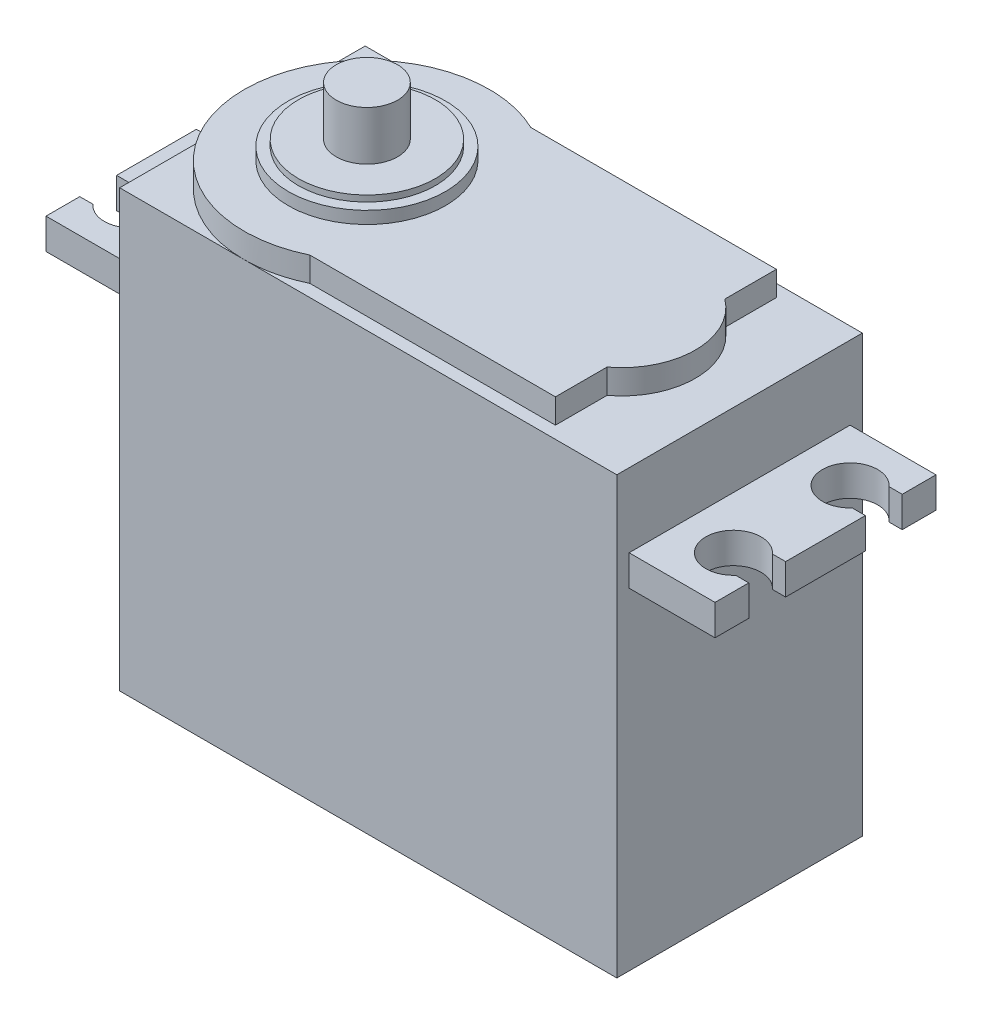
SolidWorks part; units mm, degrees
ref_plane "Front" through (0, 0, 0) normal (0, 0, 1) x (1, 0, 0)
ref_plane "Top" through (0, 0, 0) normal (0, 1, 0) x (1, 0, 0)
ref_plane "Right" through (0, 0, 0) normal (1, 0, 0) x (0, 0, -1)
sketch "Sketch1" plane through (0, 0, 0) normal (0, 1, 0) x (1, 0, 0)
  line L0 (-20.25, 10) -> (20.25, -10) construction
  line L1 (-20.25, -10) -> (20.25, -10)
  line L2 (-20.25, -10) -> (-20.25, 10)
  line L3 (-20.25, 10) -> (20.25, 10)
  line L4 (20.25, -10) -> (20.25, 10)
  line L5 (20.25, 10) -> (-20.25, -10) construction
  dimension "D1" = 20
  dimension "D2" = 40.5
extrude "Boss-Extrude1" add sketch "Sketch1" along normal blind 35.5
sketch "Sketch2" plane through (0, 35.5, 0) normal (0, 1, 0) x (1, 0, 0)
  line L0 (-5.75, -9) -> (14.25, -9)
  line L1 (14.25, -9) -> (14.25, -4.8)
  line L2 (-5.75, 9) -> (14.25, 9)
  line L3 (14.25, 9) -> (14.25, 4.8)
  line L4 (20.25, 10) -> (-20.25, 10) construction
  line L5 (-20.25, -10) -> (20.25, -10) construction
  line L6 (20.25, -10) -> (20.25, 10) construction
  line L7 (20.25, -10) -> (20.25, 10) construction
  arc A0 (-5.75, 9) -> (-5.75, -9) centre (-10.1089, 0) ccw
  arc A1 (14.25, 4.8) -> (14.25, -4.8) centre (10.65, 0) cw
  point P6 (0, 10)
  point P12 (16.65, 0)
  point P13 (20.25, 0)
  dimension "D1" = 1
  dimension "D3" = 4.2
  dimension "D2" = 1
  dimension "D4" = 3.6
  dimension "D5" = 20
  dimension "D6" = 6
extrude "Boss-Extrude2" add sketch "Sketch2" along normal blind 2
sketch "Sketch3" plane through (0, 37.5, 0) normal (0, 1, 0) x (1, 0, 0)
  circle A0 centre (-10.1089, 0) radius 6.4
  arc A1 (-10.1089, 10) -> (-10.1089, -10) centre (-10.1089, 0) ccw construction
  dimension "D1" = 12.8
extrude "Boss-Extrude3" add sketch "Sketch3" along normal blind 1
sketch "Sketch4" plane through (0, 38.5, 0) normal (0, 1, 0) x (1, 0, 0)
  circle A0 centre (-10.1089, 0) radius 5.575
  circle A1 centre (-10.1089, 0) radius 6.4 construction
  dimension "D1" = 11.15
extrude "Boss-Extrude4" add sketch "Sketch4" along normal blind 0.5
ref_plane "Plane1" through (0, 29.5, 0) normal (0, 1, 0) x (1, 0, 0)
sketch "Sketch5" plane through (0, 29.5, 0) normal (0, 1, 0) x (1, 0, 0)
  line L0 (20.25, 9) -> (27.25, 9)
  line L1 (20.25, -10) -> (20.25, 10) construction
  line L2 (27.25, 0) -> (27.25, 3.25)
  line L3 (20.25, 0) -> (27.25, 0)
  line L4 (20.25, 0) -> (20.25, 9)
  line L5 (20.25, 10) -> (-10.1089, 10) construction
  line L7 (24.5, 7) -> (24.5, 9) construction
  line L8 (27.25, 6.25) -> (27.25, 9)
  line L9 (26.1771, 6.25) -> (27.25, 6.25)
  line L10 (26.1771, 3.25) -> (27.25, 3.25)
  arc A0 (26.1771, 6.25) -> (26.1771, 3.25) centre (24.5, 4.75) ccw
  point P9 (22.25, 4.75)
  dimension "D4" = 4.5
  dimension "D5" = 2
  dimension "D1" = 1
  dimension "D2" = 9
  dimension "D3" = 7
  dimension "D6" = 3
  dimension "D7" = 2
extrude "Boss-Extrude5" add sketch "Sketch5" against normal blind 2.5
mirror "Mirror1" about plane through (0, 0, 0) normal (1, 0, 0) of "Boss-Extrude5"
mirror "Mirror2" about plane through (0, 0, 0) normal (0, 0, 1) of "Boss-Extrude5", "Mirror1"
sketch "Sketch6" plane through (0, 39, 0) normal (0, 1, 0) x (1, 0, 0)
  circle A0 centre (-10.1089, 0) radius 2.5
  dimension "D1" = 5
extrude "Boss-Extrude6" add sketch "Sketch6" along normal blind 4
